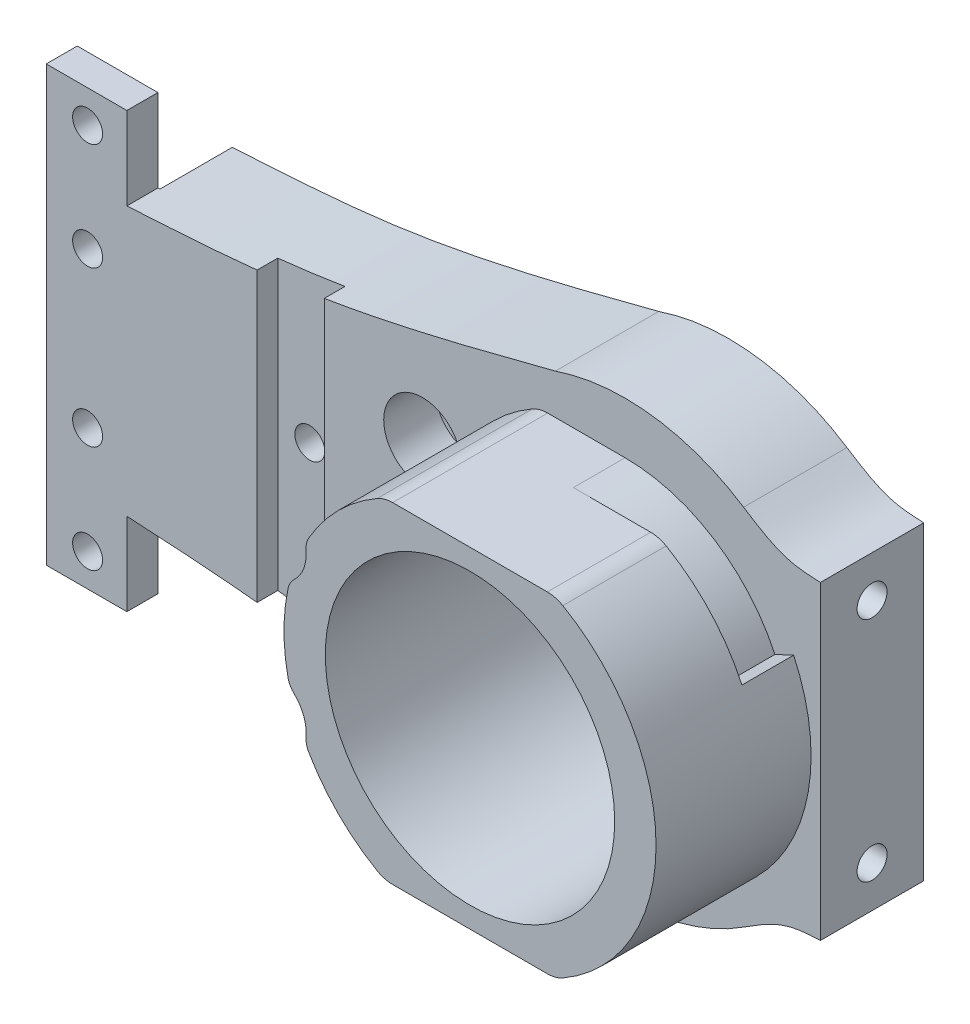
SolidWorks part; units mm, degrees
ref_plane "Front Plane" through (0, 0, 0) normal (0, 0, 1) x (1, 0, 0)
ref_plane "Top Plane" through (0, 0, 0) normal (0, 1, 0) x (1, 0, 0)
ref_plane "Right Plane" through (0, 0, 0) normal (1, 0, 0) x (0, 0, -1)
sketch "Sketch1" plane through (0, 0, 0) normal (0, 0, 1) x (1, 0, 0)
  line L0 (-30, 21) -> (-22.2, 21)
  line L1 (44.9, 15) -> (44.9, -15)
  line L2 (-22.2, 21) -> (-22.2, 13)
  line L3 (-30, -21) -> (-30, 21)
  line L4 (-30, 0) -> (0, 0) construction
  line L5 (0, 0) -> (44.9, 0) construction
  line L6 (-30, -21) -> (-22.2, -21)
  line L7 (-22.2, -21) -> (-22.2, -13)
  circle A0 centre (26, 0) radius 14
  arc A1 (19.2579, -19.8883) -> (37.4703, -17.5907) centre (26, 0) ccw
  arc A2 (37.4703, 17.5907) -> (19.2579, 19.8883) centre (26, 0) ccw
  spline S0 degree 3 poles (-22.2, 13) (-17.0873, 13.2934) (-3.0476, 14.0991) (10.5879, 17.6381) (19.2579, 19.8883) knots 0 0 0 0 0.364161 1 1 1 1
  spline S1 degree 3 poles (-22.2, -13) (-17.0873, -13.2934) (-3.0476, -14.0991) (10.5879, -17.6381) (19.2579, -19.8883) knots 0 0 0 0 0.364161 1 1 1 1
  spline S2 degree 3 poles (44.9, 15) (43.9598, 15.0415) (41.2679, 15.1604) (38.9674, 16.6326) (37.4703, 17.5907) knots 0 0 0 0 0.349252 1 1 1 1
  spline S3 degree 3 poles (44.9, -15) (43.9598, -15.0415) (41.2679, -15.1604) (38.9674, -16.6326) (37.4703, -17.5907) knots 0 0 0 0 0.349252 1 1 1 1
  dimension "D4" = 28
  dimension "D5" = 42
  dimension "D1" = 74.9
  dimension "D2" = 42
  dimension "D3" = 30
  dimension "D6" = 56
  dimension "D7" = 30
  dimension "D8" = 7.8
  dimension "D9" = 8
extrude "Extrude1" add sketch "Sketch1" along normal blind 10
sketch "Sketch3" plane through (0, 0, 10) normal (0, 0, 1) x (1, 0, 0)
  circle A0 centre (26, 0) radius 18
  circle A1 centre (26, 0) radius 14
  dimension "D1" = 36
extrude "Extrude2" add sketch "Sketch3" along normal blind 15
sketch "Sketch4" plane through (0, 0, 0) normal (0, 0, -1) x (-1, 0, 0)
  line L0 (30, 21) -> (30, -21) construction
  line L1 (30, 23.4126) -> (22, 23.4126)
  line L2 (30, 23.4126) -> (30, -25.9867)
  line L3 (30, -25.9867) -> (22, -25.9867)
  line L4 (22, 23.4126) -> (22, -25.9867)
  dimension "D1" = 8
extrude "Extrude3" cut sketch "Sketch4" against normal blind 7
hole_wizard "CBORE for M3 Pan Head Machine Screw1" positions "3DSketch1" profile "Sketch5" counterbore size "M3" standard "Ansi Metric" end condition through all
sketch3d "3DSketch1"
  line L0 (6.4, 7.5, 10) -> (6.4, -7.5, 10) construction
  line L3 (6.4, 0, 10) -> (0, 0, 10) construction
  line L4 (-30, 21, 10) -> (-30, -21, 10) construction
  point P0 (6.4, 7.5, 10)
  point P2 (6.4, -7.5, 10)
  dimension "D1" = 7.5
  dimension "D2" = 7.5
  dimension "D3" = 36.4
sketch "Sketch5" plane through (6.4, 7.5, 10) normal (1, 0, 0) x (0, -1, 0)
  line L0 (0, 0) -> (0, 10)
  line L1 (0, 10) -> (1.8, 10)
  line L3 (1.8, 10) -> (1.8, 5)
  line L4 (1.8, 5) -> (3.75, 5)
  line L5 (3.75, 5) -> (3.75, 0)
  line L7 (3.75, 0) -> (0, 0)
  line L11 (0, -6.35) -> (0, 107.95) construction
  dimension "Thru Hole Dia." = 3.6
  dimension "Thru Hole Depth" = 10
  dimension "C'Bore Dia." = 7.5
  dimension "C'Bore Depth" = 5
sketch "Sketch6" plane through (0, 0, 10) normal (0, 0, 1) x (1, 0, 0)
  circle A0 centre (6.4, 7.5) radius 3.75
  circle A1 centre (6.4, -7.5) radius 3.75
  circle A2 centre (6.4, 7.5) radius 3.75 construction
extrude "Extrude4" cut sketch "Sketch6" along normal blind 20
fillet "Fillet1" radius 2 4 edges at (10.0529, -8.348, 17.5) (8.5537, 4.4301, 17.5) (10.0529, 8.348, 17.5) (8.5537, -4.4301, 17.5)
sketch "Sketch8" plane through (0, 0, 25) normal (0, 0, 1) x (1, 0, 0)
  line L0 (0, 0) -> (9, 0) construction
  line L1 (17.7538, 16) -> (34.2462, 16)
  line L2 (17.7538, 16) -> (17.7538, 23.4488)
  line L3 (17.7538, 23.4488) -> (34.2462, 23.4488)
  line L4 (34.2462, 16) -> (34.2462, 23.4488)
  line L5 (26, 0) -> (26, 26.3314) construction
  line L6 (17.7538, -23.4488) -> (34.2462, -23.4488)
  line L7 (34.2462, -16) -> (34.2462, -23.4488)
  line L8 (17.7538, -16) -> (34.2462, -16)
  line L9 (17.7538, -16) -> (17.7538, -23.4488)
  circle A0 centre (26, 0) radius 18 construction
  point P13 (26, 16)
  dimension "D1" = 16
extrude "Extrude5" cut sketch "Sketch8" against normal up to surface (15 mm away) up to face at (4.5821, 0.3581, 10)
fillet "Fillet2" radius 3 4 edges at (17.7538, -16, 17.5) (34.2462, -16, 17.5) (34.2462, 16, 17.5) (17.7538, 16, 17.5)
sketch "Sketch11" plane through (0, 0, 10) normal (0, 0, 1) x (1, 0, 0)
  line L0 (18.5167, 16) -> (33.4833, 16) construction
  line L1 (26, 16) -> (26, 19)
  line L2 (40.4989, 6.7663) -> (43.2174, 8.0349)
  line L3 (26, -16) -> (26, -19)
  line L5 (40.4989, 6.7663) -> (8.7826, -8.0349) construction
  line L6 (8.7826, -8.0349) -> (11.5011, -6.7663)
  arc A0 (11.5011, -6.7663) -> (26, -16) centre (26, 0) ccw
  arc A1 (8.7826, -8.0349) -> (26, -19) centre (26, 0) ccw
  arc A2 (40.4989, 6.7663) -> (26, 16) centre (26, 0) ccw
  arc A3 (43.2174, 8.0349) -> (26, 19) centre (26, 0) ccw
  dimension "D1" = 35
extrude "Extrude8" cut sketch "Sketch11" along normal blind 5
hole_wizard "Ø2.9 (2.9) Diameter Hole1" positions "3DSketch2" profile "Sketch13" hole size "Ø2.9" standard "Ansi Metric"
sketch3d "3DSketch2"
  line L0 (-26, -21, 10) -> (-26, 21, 10) construction
  line L1 (-30, -21, 10) -> (-22.2, -21, 10) construction
  line L2 (-22.2, 21, 10) -> (-30, 21, 10) construction
  line L6 (-30, 21, 10) -> (-30, -21, 10) construction
  point P0 (-26, -17.85, 10)
  point P2 (-26, -7.5, 10)
  point P4 (-26, 7.5, 10)
  point P6 (-26, 17.85, 10)
  point P22 (-26, 0, 10)
  dimension "D1" = 15
  dimension "D2" = 7.5
  dimension "D3" = 3.15
  dimension "D4" = 3.15
  dimension "D5" = 4
sketch "Sketch13" plane through (-26, -17.85, 10) normal (1, 0, 0) x (0, -1, 0)
  line L0 (0, 0) -> (0, 10)
  line L1 (0, 10) -> (1.45, 10)
  line L2 (1.45, 10) -> (1.45, 0)
  line L5 (1.45, 0) -> (0, 0)
  line L10 (0, 10) -> (-1.45, 10) construction
  line L11 (0, -6.35) -> (0, 107.95) construction
  dimension "Hole Dia." = 2.9
  dimension "Hole Depth" = 10
  dimension "Drill Angle" = 180
sketch "Sketch14" plane through (0, 0, 10) normal (0, 0, 1) x (1, 0, 0)
  line L0 (-30, 21) -> (-30, -21) construction
  line L1 (-3.1, -23.334) -> (-9.6, -23.334)
  line L2 (-3.1, -23.334) -> (-3.1, 21.2199)
  line L3 (-3.1, 21.2199) -> (-9.6, 21.2199)
  line L4 (-9.6, -23.334) -> (-9.6, 21.2199)
  dimension "D1" = 6.5
  dimension "D2" = 20.4
extrude "Extrude9" cut sketch "Sketch14" against normal blind 2
sketch "Sketch15" plane through (0, 0, 8) normal (0, 0, 1) x (1, 0, 0)
  line L0 (-6.5, -14.2974) -> (-6.5, 14.2974) construction
  line L1 (-9.6, 13.9272) -> (-9.6, -13.9272) construction
  circle A0 centre (-6.5, 0) radius 1.45
  spline S0 degree 3 poles (-9.6, -13.9272) (-8.7037, -14.0224) (-6.5313, -14.276) (-4.3688, -14.5963) (-3.1, -14.8043) knots 0.299863 0.299863 0.299863 0.299863 0.364161 0.455943 0.455943 0.455943 0.455943 construction
  spline S1 degree 3 poles (-3.1, 14.8043) (-4.3688, 14.5963) (-6.5313, 14.276) (-8.7037, 14.0224) (-9.6, 13.9272) knots 0.544057 0.544057 0.544057 0.544057 0.635839 0.700137 0.700137 0.700137 0.700137 construction
  point P8 (-6.5, 0)
  dimension "D1" = 2.9
  dimension "D2" = 3.1
extrude "Extrude10" cut sketch "Sketch15" against normal blind 10
sketch "Sketch16" plane through (44.9, 0, 0) normal (1, 0, 0) x (0, 0, -1)
  line L0 (-5, -15) -> (-5, 15) construction
  line L2 (-10, 15) -> (0, 15) construction
  line L3 (-10, -15) -> (-10, 15) construction
  circle A0 centre (-5, -11) radius 1.45
  circle A1 centre (-5, 11) radius 1.45
  dimension "D1" = 2.9
  dimension "D2" = 4
  dimension "D3" = 4
  dimension "D4" = 5
extrude "Extrude11" cut sketch "Sketch16" against normal blind 6
